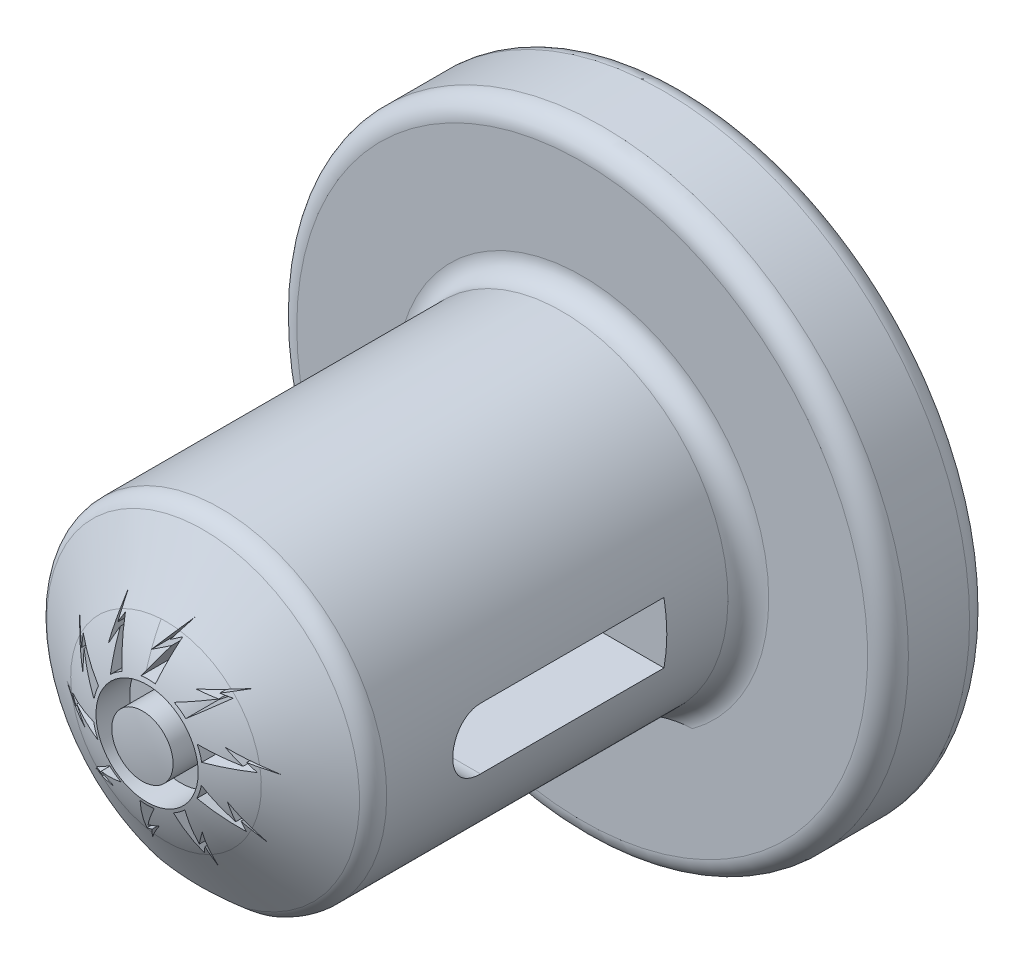
SolidWorks part; units mm, degrees
ref_plane "Alzado" through (0, 0, 0) normal (0, 0, 1) x (1, 0, 0)
ref_plane "Planta" through (0, 0, 0) normal (0, 1, 0) x (1, 0, 0)
ref_plane "Vista lateral" through (0, 0, 0) normal (1, 0, 0) x (0, 0, -1)
sketch "Croquis1" plane through (0, 0, 0) normal (0, 0, 1) x (1, 0, 0)
  line L0 (3.4463, -7.3855) -> (-3.4463, -7.3855)
  line L1 (2.7, -4.3855) -> (-2.7, -4.3855)
  arc A0 (2.7, -4.3855) -> (-2.7, -4.3855) centre (0, 0) ccw
  arc A1 (3.4463, -7.3855) -> (-3.4463, -7.3855) centre (0, 0) ccw
  point P7 (0, -4.3855)
  dimension "D1" = 10.3
  dimension "D2" = 5.4
  dimension "D3" = 3
extrude "Saliente-Extruir1" add sketch "Croquis1" along normal blind 23.3
sketch "Croquis2" plane through (0, 0, 0) normal (0, 0, -1) x (-1, 0, 0)
  line L0 (2.7, -4.3855) -> (-2.7, -4.3855) construction
  line L1 (2.7, -4.3855) -> (-2.7, -4.3855)
  circle A0 centre (0, 0) radius 15
  arc A1 (2.7, -4.3855) -> (-2.7, -4.3855) centre (0, 0) ccw construction
  arc A2 (2.7, -4.3855) -> (-2.7, -4.3855) centre (0, 0) ccw
  dimension "D1" = 30
extrude "Saliente-Extruir2" add sketch "Croquis2" against normal blind 5
sketch "Croquis3" plane through (0, 0, 0) normal (1, 0, 0) x (0, 0, -1)
  line L0 (-23.3, 0) -> (-23.3, 8.15)
  line L2 (-23.3, 8.15) -> (-25.4124, 4.6757)
  line L3 (-26.7223, 0) -> (-23.3, 0)
  arc A0 (-25.4124, 4.6757) -> (-26.7223, 0) centre (-17.7223, 0) ccw
  dimension "D2" = 9
  dimension "D1" = 31.3
revolve "Revolución1" add sketch "Croquis3" angle 360 about L3
sketch "Croquis4" plane through (0, 0, 23.3) normal (0, 0, -1) x (-1, 0, 0)
  line L1 (3.4463, -7.3855) -> (-3.4463, -7.3855)
  line L2 (3.4463, -7.3855) -> (-3.4463, -7.3855)
  arc A1 (-3.4463, -7.3855) -> (3.4463, -7.3855) centre (0, 0) ccw
  arc A2 (-3.4463, -7.3855) -> (3.4463, -7.3855) centre (0, 0) ccw
  dimension "D1" = 0
extrude "Cortar-Extruir1" cut sketch "Croquis4" against normal up to next
fillet "Redondeo3" radius 1 4 edges at (-15, 0, 0) (-15, 0, 5) (0, 8.15, 5) (0, 8.15, 23.3)
fillet "Redondeo2" radius 1 2 edges at (0, -4.3855, 0) (0, 5.15, 0)
ref_plane "Plano1" through (0, 0, 26.7223) normal (0, 0, 1) x (1, 0, 0)
sketch "Croquis5" plane through (0, 0, 26.7223) normal (0, 0, 1) x (1, 0, 0)
  line L0 (1.3026, 2.3441) -> (2.8816, 2.9738)
  line L1 (-0.324, 2.662) -> (0.5833, 4.0996)
  line L2 (0.5833, 4.0996) -> (-0.19, 3.662)
  line L3 (-0.19, 3.662) -> (1.0396, 5.192)
  line L4 (1.0396, 5.192) -> (0.4463, 4.2519)
  line L5 (0.4463, 4.2519) -> (0.876, 4.4951)
  line L6 (0.876, 4.4951) -> (0.376, 2.662)
  line L7 (2.8816, 2.9738) -> (1.9987, 3.0743)
  line L8 (1.9987, 3.0743) -> (3.8929, 3.5894)
  line L9 (3.8929, 3.5894) -> (2.8603, 3.1775)
  line L10 (2.8603, 3.1775) -> (3.3508, 3.1217)
  line L11 (3.3508, 3.1217) -> (1.8689, 1.9326)
  line L12 (2.4316, 1.1308) -> (4.0792, 0.7121)
  line L13 (4.0792, 0.7121) -> (3.4241, 1.3124)
  line L14 (3.4241, 1.3124) -> (5.2592, 0.6157)
  line L15 (5.2592, 0.6157) -> (4.1817, 0.8895)
  line L16 (4.1817, 0.8895) -> (4.5457, 0.5559)
  line L17 (4.5457, 0.5559) -> (2.6479, 0.465)
  line L18 (2.6319, -0.5144) -> (3.7187, -1.8216)
  line L19 (3.7187, -1.8216) -> (3.5415, -0.9509)
  line L20 (3.5415, -0.9509) -> (4.6166, -2.5932)
  line L21 (4.6166, -2.5932) -> (3.9059, -1.7384)
  line L22 (3.9059, -1.7384) -> (4.0044, -2.2222)
  line L23 (4.0044, -2.2222) -> (2.4155, -1.1802)
  line L24 (1.8268, -1.9632) -> (1.9378, -3.6595)
  line L25 (1.9378, -3.6595) -> (2.3062, -2.8509)
  line L26 (2.3062, -2.8509) -> (2.2107, -4.8115)
  line L27 (2.2107, -4.8115) -> (2.1381, -3.7022)
  line L28 (2.1381, -3.7022) -> (1.9334, -4.1515)
  line L29 (1.9334, -4.1515) -> (1.2605, -2.3746)
  line L30 (0.324, -2.662) -> (-0.5833, -4.0996)
  line L31 (-0.5833, -4.0996) -> (0.19, -3.662)
  line L32 (0.19, -3.662) -> (-1.0396, -5.192)
  line L33 (-1.0396, -5.192) -> (-0.4463, -4.2519)
  line L34 (-0.4463, -4.2519) -> (-0.876, -4.4951)
  line L35 (-0.876, -4.4951) -> (-0.376, -2.662)
  line L36 (-1.3026, -2.3441) -> (-2.8816, -2.9738)
  line L37 (-2.8816, -2.9738) -> (-1.9987, -3.0743)
  line L38 (-1.9987, -3.0743) -> (-3.8929, -3.5894)
  line L39 (-3.8929, -3.5894) -> (-2.8603, -3.1775)
  line L40 (-2.8603, -3.1775) -> (-3.3508, -3.1217)
  line L41 (-3.3508, -3.1217) -> (-1.8689, -1.9326)
  line L42 (-2.4316, -1.1308) -> (-4.0792, -0.7121)
  line L43 (-4.0792, -0.7121) -> (-3.4241, -1.3124)
  line L44 (-3.4241, -1.3124) -> (-5.2592, -0.6157)
  line L45 (-5.2592, -0.6157) -> (-4.1817, -0.8895)
  line L46 (-4.1817, -0.8895) -> (-4.5457, -0.5559)
  line L47 (-4.5457, -0.5559) -> (-2.6479, -0.465)
  line L48 (-2.6319, 0.5144) -> (-3.7187, 1.8216)
  line L49 (-3.7187, 1.8216) -> (-3.5415, 0.9509)
  line L50 (-3.5415, 0.9509) -> (-4.6166, 2.5932)
  line L51 (-4.6166, 2.5932) -> (-3.9059, 1.7384)
  line L52 (-3.9059, 1.7384) -> (-4.0044, 2.2222)
  line L53 (-4.0044, 2.2222) -> (-2.4155, 1.1802)
  line L54 (-1.8268, 1.9632) -> (-1.9378, 3.6595)
  line L55 (-1.9378, 3.6595) -> (-2.3062, 2.8509)
  line L56 (-2.3062, 2.8509) -> (-2.2107, 4.8115)
  line L57 (-2.2107, 4.8115) -> (-2.1381, 3.7022)
  line L58 (-2.1381, 3.7022) -> (-1.9334, 4.1515)
  line L59 (-1.9334, 4.1515) -> (-1.2605, 2.3746)
  circle A0 centre (0.026, -0.0152) radius 1.5
  circle A1 centre (0.026, -0.0152) radius 2.5
  arc A2 (0.376, 2.662) -> (-0.324, 2.662) centre (0.026, -0.0152) ccw
  arc A3 (1.8689, 1.9326) -> (1.3026, 2.3441) centre (0.0121, -0.0276) ccw
  arc A4 (2.6479, 0.465) -> (2.4316, 1.1308) centre (-0.0064, -0.0294) ccw
  arc A5 (2.4155, -1.1802) -> (2.6319, -0.5144) centre (-0.0225, -0.02) ccw
  arc A6 (1.2605, -2.3746) -> (1.8268, -1.9632) centre (-0.03, -0.003) ccw
  arc A7 (-0.376, -2.662) -> (0.324, -2.662) centre (-0.026, 0.0152) ccw
  arc A8 (-1.8689, -1.9326) -> (-1.3026, -2.3441) centre (-0.0121, 0.0276) ccw
  arc A9 (-2.6479, -0.465) -> (-2.4316, -1.1308) centre (0.0064, 0.0294) ccw
  arc A10 (-2.4155, 1.1802) -> (-2.6319, 0.5144) centre (0.0225, 0.02) ccw
  arc A11 (-1.2605, 2.3746) -> (-1.8268, 1.9632) centre (0.03, 0.003) ccw
  point P1 (0.026, 2.6848)
  point P4 (0.026, -0.0152)
  point P11 (0.026, -0.0152)
  point P38 (0.026, -0.0152)
  point P91 (0, 0)
  dimension "D1" = 3
  dimension "D12" = 2.7
  dimension "D9" = 5
  dimension "D2" = 0.2
  dimension "D3" = 1.9
  dimension "D4" = 1.7
  dimension "D5" = 0.7
  dimension "D6" = 0.5
  dimension "D7" = 1
  dimension "D8" = 2.53
  dimension "D10" = 0.566
  dimension "D11" = 0.6637
  dimension "D13" = 0.026
  dimension "D14" = 10
  dimension "D15" = 0.0064
extrude "Cortar-Extruir2" cut sketch "Croquis5" against normal blind 2
chamfer "Chaflán1" distance 0.5 angle 45 1 edges at (0, 5.15, 23.3)
ref_plane "Plano2" through (8.15, 0, 0) normal (1, 0, 0) x (0, 0, -1)
sketch "Croquis6" plane through (8.15, 0, 0) normal (1, 0, 0) x (0, 0, -1)
  line L0 (-18, 0) -> (-5, 0) construction
  line L1 (-18, 1.5) -> (-5, 1.5) construction
  line L2 (-18, -1.5) -> (-5, -1.5) construction
  line L3 (-23.3, -4.3855) -> (-23.3, 4.65) construction
  line L4 (-9, -1.5) -> (-9, 1.5)
  line L5 (-9, 1.5) -> (-18, 1.5)
  line L6 (-18, -1.5) -> (-9, -1.5)
  line L8 (-5, -7.3855) -> (-5, -8.15) construction
  arc A0 (-18, 1.5) -> (-18, -1.5) centre (-18, 0) ccw construction
  arc A1 (-5, -1.5) -> (-5, 1.5) centre (-5, 0) ccw construction
  arc A2 (-18, 1.5) -> (-18, -1.5) centre (-18, 0) ccw
  point P3 (-11.5, 0)
  point P8 (-19.5, 0)
  point P11 (-3.5, 0)
  dimension "D1" = 3
  dimension "D2" = 3.8
  dimension "D3" = 16
  dimension "D4" = 4
extrude "Cortar-Extruir3" cut sketch "Croquis6" against normal up to next
